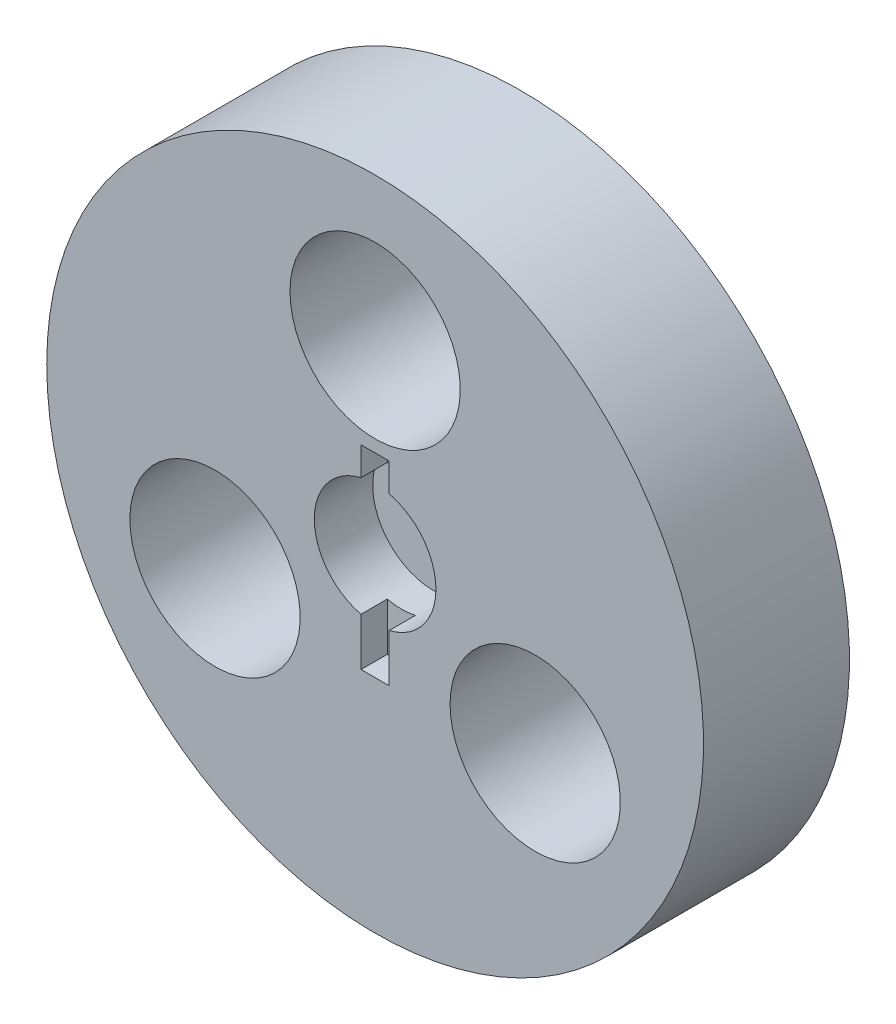
SolidWorks part; units mm, degrees
material "Teak"
ref_plane "Front Plane" through (0, 0, 0) normal (0, 0, 1) x (1, 0, 0)
ref_plane "Top Plane" through (0, 0, 0) normal (0, 1, 0) x (1, 0, 0)
ref_plane "Right Plane" through (0, 0, 0) normal (1, 0, 0) x (0, 0, -1)
sketch "Sketch1" plane through (0, 0, 0) normal (0, 0, 1) x (1, 0, 0)
  line L0 (0, 0) -> (20.8972, -12.065) construction
  line L1 (0, 42.8625) -> (0, -42.8625) construction
  line L2 (0, 0) -> (-20.8972, -12.065) construction
  line L3 (0, 24.13) -> (0, 0)
  circle A0 centre (0, 0) radius 42.8625
  circle A1 centre (0, 24.13) radius 11.1125
  circle A2 centre (-20.8972, -12.065) radius 11.1125
  circle A3 centre (20.8972, -12.065) radius 11.1125
  dimension "D3" = 85.725
  dimension "D5" = 22.225
  dimension "D1" = 120
  dimension "D2" = 120
  dimension "D4" = 24.13
extrude "Boss-Extrude1" add sketch "Sketch1" along normal mid plane 19.05 contours A0 A3 A2 A1 region at (-41.6502, 0, 0)
sketch "Sketch2" plane through (0, 0, 9.525) normal (0, 0, 1) x (1, 0, 0)
  circle A0 centre (0, 0) radius 7.9375
  dimension "D1" = 15.875
extrude "Cut-Extrude1" cut sketch "Sketch2" against normal blind 7.62
sketch "Sketch3" plane through (0, 0, 9.525) normal (0, 0, 1) x (1, 0, 0)
  line L0 (0, 11.43) -> (0, -13.97) construction
  line L1 (1.8415, 11.43) -> (-1.8415, 11.43)
  line L2 (1.8415, 11.43) -> (1.8415, -13.97)
  line L3 (1.8415, -13.97) -> (-1.8415, -13.97)
  line L4 (-1.8415, 11.43) -> (-1.8415, -13.97)
  circle A0 centre (0, 24.13) radius 11.1125 construction
  dimension "D1" = 3.683
  dimension "D2" = 25.4
  dimension "D3" = 12.7
extrude "Cut-Extrude2" cut sketch "Sketch3" against normal blind 3.429
